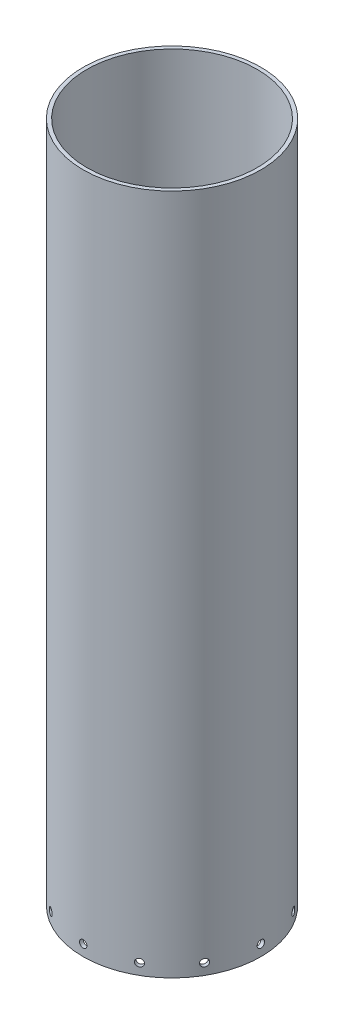
SolidWorks part; units mm, degrees
material "Polycarbonate"
ref_plane "Front Plane" through (0, 0, 0) normal (0, 0, 1) x (1, 0, 0)
ref_plane "Top Plane" through (0, 0, 0) normal (0, 1, 0) x (1, 0, 0)
ref_plane "Right Plane" through (0, 0, 0) normal (1, 0, 0) x (0, 0, -1)
sketch "Sketch2" plane through (0, 0, 0) normal (0, 1, 0) x (1, 0, 0)
  circle A0 centre (0, 0) radius 73.025
  circle A1 centre (0, 0) radius 76.2
  dimension "D1" = 146.05
  dimension "D2" = 152.4
extrude "Boss-Extrude1" add sketch "Sketch2" along normal blind 584.2
sketch "Sketch3" plane through (0, 0, 0) normal (0, 0, 1) x (1, 0, 0)
  line L0 (0, 0) -> (0, 235.745) construction
  line L1 (-76.2, 0) -> (76.2, 0) construction
  circle A0 centre (0, 9.525) radius 3.175
  dimension "D1" = 9.525
extrude "Cut-Extrude1" cut sketch "Sketch3" against normal through all
ref_axis "Axis1" through (0, 0, 0) along (0, 1, 0)
pattern_circular "CirPattern1" count 12 over 360 about axis through (0, 0, 0) along (0, 1, 0) of "Cut-Extrude1"
